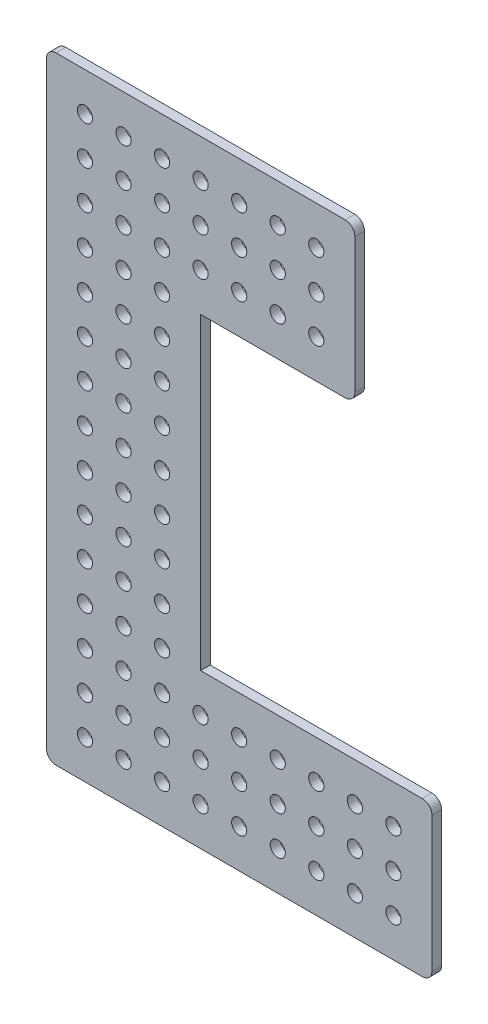
SolidWorks part; units mm, degrees
ref_plane "Front Plane" through (0, 0, 0) normal (0, 0, 1) x (1, 0, 0)
ref_plane "Top Plane" through (0, 0, 0) normal (0, 1, 0) x (1, 0, 0)
ref_plane "Right Plane" through (0, 0, 0) normal (1, 0, 0) x (0, 0, -1)
sketch "Sketch1" plane through (0, 0, 0) normal (0, 0, 1) x (1, 0, 0)
  line L0 (23.16, 167.0479) -> (26.335, 167.0479)
  line L1 (-24.465, 14.6479) -> (99.36, 14.6479)
  line L2 (-24.465, 14.6479) -> (-24.465, -32.9771)
  line L3 (-21.29, -36.1521) -> (99.36, -36.1521)
  line L4 (102.535, 11.4729) -> (102.535, -32.9771)
  line L5 (-21.29, 167.0479) -> (23.16, 167.0479)
  line L6 (-24.465, 163.8729) -> (-24.465, 14.6479)
  line L7 (-24.465, 14.6479) -> (26.335, 14.6479)
  line L8 (26.335, 163.8729) -> (26.335, 14.6479)
  line L9 (26.335, 167.0479) -> (26.335, 163.8729)
  arc A0 (-24.465, -32.9771) -> (-21.29, -36.1521) centre (-21.29, -32.9771) ccw
  arc A1 (99.36, -36.1521) -> (102.535, -32.9771) centre (99.36, -32.9771) ccw
  arc A2 (99.36, 14.6479) -> (102.535, 11.4729) centre (99.36, 11.4729) cw
  arc A4 (-21.29, 167.0479) -> (-24.465, 163.8729) centre (-21.29, 163.8729) ccw
  point P10 (-24.465, -36.1521)
  point P13 (102.535, -36.1521)
  point P16 (102.535, 14.6479)
  point P19 (26.335, 167.0479)
  point P22 (-24.465, 167.0479)
  dimension "D5" = 3.175
  dimension "D1" = 50.8
  dimension "D2" = 50.8
  dimension "D3" = 127
  dimension "D4" = 152.4
extrude "Boss-Extrude1" add sketch "Sketch1" along normal blind 3.175 contours L8 L5 L6 L1 | L4 L1 L2 L3 region at (0.9419, 90.8268, 0) region at (39.0139, -10.7439, 0)
sketch "Sketch2" plane through (0, 0, 3.175) normal (0, 0, 1) x (1, 0, 0)
  line L0 (-24.465, 163.8729) -> (-24.465, -32.9771) construction
  line L1 (-21.29, 167.0479) -> (26.335, 167.0479) construction
  line L2 (102.535, 11.4729) -> (102.535, -32.9771) construction
  line L3 (-21.29, -36.1521) -> (99.36, -36.1521) construction
  circle A0 centre (-11.765, 154.3479) radius 2.5
  circle A1 centre (89.835, -23.4521) radius 2.5
  circle A2 centre (0.935, 154.3479) radius 2.5
  circle A3 centre (13.635, 154.3479) radius 2.5
  circle A4 centre (0.935, 141.6479) radius 2.5
  circle A5 centre (13.635, 141.6479) radius 2.5
  circle A6 centre (0.935, 128.9479) radius 2.5
  circle A7 centre (13.635, 128.9479) radius 2.5
  circle A8 centre (0.935, 116.2479) radius 2.5
  circle A9 centre (13.635, 116.2479) radius 2.5
  circle A10 centre (0.935, 103.5479) radius 2.5
  circle A11 centre (13.635, 103.5479) radius 2.5
  circle A12 centre (0.935, 90.8479) radius 2.5
  circle A13 centre (13.635, 90.8479) radius 2.5
  circle A14 centre (0.935, 78.1479) radius 2.5
  circle A15 centre (13.635, 78.1479) radius 2.5
  circle A16 centre (0.935, 65.4479) radius 2.5
  circle A17 centre (13.635, 65.4479) radius 2.5
  circle A18 centre (0.935, 52.7479) radius 2.5
  circle A19 centre (13.635, 52.7479) radius 2.5
  circle A20 centre (-11.765, 141.6479) radius 2.5
  circle A21 centre (-11.765, 128.9479) radius 2.5
  circle A22 centre (-11.765, 116.2479) radius 2.5
  circle A23 centre (-11.765, 103.5479) radius 2.5
  circle A24 centre (-11.765, 90.8479) radius 2.5
  circle A25 centre (-11.765, 78.1479) radius 2.5
  circle A26 centre (-11.765, 65.4479) radius 2.5
  circle A27 centre (-11.765, 52.7479) radius 2.5
  circle A28 centre (77.135, -23.4521) radius 2.5
  circle A29 centre (64.435, -23.4521) radius 2.5
  circle A30 centre (51.735, -23.4521) radius 2.5
  circle A31 centre (39.035, -23.4521) radius 2.5
  circle A32 centre (26.335, -23.4521) radius 2.5
  circle A33 centre (77.135, -10.7521) radius 2.5
  circle A34 centre (64.435, -10.7521) radius 2.5
  circle A35 centre (51.735, -10.7521) radius 2.5
  circle A36 centre (39.035, -10.7521) radius 2.5
  circle A37 centre (26.335, -10.7521) radius 2.5
  circle A38 centre (77.135, 1.9479) radius 2.5
  circle A39 centre (64.435, 1.9479) radius 2.5
  circle A40 centre (51.735, 1.9479) radius 2.5
  circle A41 centre (39.035, 1.9479) radius 2.5
  circle A42 centre (26.335, 1.9479) radius 2.5
  circle A43 centre (89.835, -10.7521) radius 2.5
  circle A44 centre (89.835, 1.9479) radius 2.5
  circle A45 centre (-11.765, 40.0479) radius 2.5
  circle A46 centre (0.935, 40.0479) radius 2.5
  circle A47 centre (13.635, 40.0479) radius 2.5
  circle A48 centre (-11.765, 27.3479) radius 2.5
  circle A49 centre (0.935, 27.3479) radius 2.5
  circle A50 centre (13.635, 27.3479) radius 2.5
  circle A51 centre (-11.765, 14.6479) radius 2.5
  circle A52 centre (0.935, 14.6479) radius 2.5
  circle A53 centre (13.635, 14.6479) radius 2.5
  circle A54 centre (-11.765, 1.9479) radius 2.5
  circle A55 centre (0.935, 1.9479) radius 2.5
  circle A56 centre (13.635, 1.9479) radius 2.5
  circle A57 centre (-11.765, -10.7521) radius 2.5
  circle A58 centre (0.935, -10.7521) radius 2.5
  circle A59 centre (13.635, -10.7521) radius 2.5
  circle A60 centre (-11.765, -23.4521) radius 2.5
  circle A61 centre (0.935, -23.4521) radius 2.5
  circle A62 centre (13.635, -23.4521) radius 2.5
  dimension "D1" = 5
  dimension "D4" = 5
  dimension "D2" = 12.7
  dimension "D3" = 12.7
  dimension "D5" = 12.7
  dimension "D6" = 12.7
  dimension "D7" = 3
  dimension "D9" = 15
  dimension "D8" = 6
extrude "Cut-Extrude1" cut sketch "Sketch2" against normal through all
sketch "Sketch3" plane through (0, 0, 3.175) normal (0, 0, 1) x (1, 0, 0)
  line L0 (26.335, 167.0479) -> (26.335, 14.6479) construction
  line L1 (73.96, 167.0479) -> (26.335, 167.0479)
  line L2 (77.135, 163.8729) -> (77.135, 119.4229)
  line L3 (73.96, 116.2479) -> (26.335, 116.2479)
  line L4 (26.335, 167.0479) -> (26.335, 116.2479)
  line L5 (-21.29, 167.0479) -> (26.335, 167.0479) construction
  arc A0 (77.135, 119.4229) -> (73.96, 116.2479) centre (73.96, 119.4229) cw
  arc A1 (73.96, 167.0479) -> (77.135, 163.8729) centre (73.96, 163.8729) cw
  point P10 (77.135, 116.2479)
  point P13 (77.135, 167.0479)
  dimension "D3" = 3.175
  dimension "D1" = 50.8
  dimension "D2" = 50.8
extrude "Boss-Extrude2" add sketch "Sketch3" against normal up to surface (3.175 mm away) up to face at (-9.265, 90.8479, 0)
sketch "Sketch4" plane through (0, 0, 3.175) normal (0, 0, 1) x (1, 0, 0)
  line L0 (77.135, 119.4229) -> (77.135, 163.8729) construction
  line L1 (-21.29, 167.0479) -> (73.96, 167.0479) construction
  circle A0 centre (64.435, 154.3479) radius 2.505
  circle A1 centre (51.735, 154.3479) radius 2.505
  circle A2 centre (39.035, 154.3479) radius 2.505
  circle A3 centre (26.335, 154.3479) radius 2.505
  circle A4 centre (51.735, 141.6479) radius 2.505
  circle A5 centre (39.035, 141.6479) radius 2.505
  circle A6 centre (26.335, 141.6479) radius 2.505
  circle A7 centre (51.735, 128.9479) radius 2.505
  circle A8 centre (39.035, 128.9479) radius 2.505
  circle A9 centre (26.335, 128.9479) radius 2.505
  circle A10 centre (64.435, 141.6479) radius 2.505
  circle A11 centre (64.435, 128.9479) radius 2.505
  dimension "D1" = 5.01
  dimension "D2" = 12.7
  dimension "D3" = 12.7
  dimension "D4" = 4
extrude "Cut-Extrude2" cut sketch "Sketch4" against normal through all
